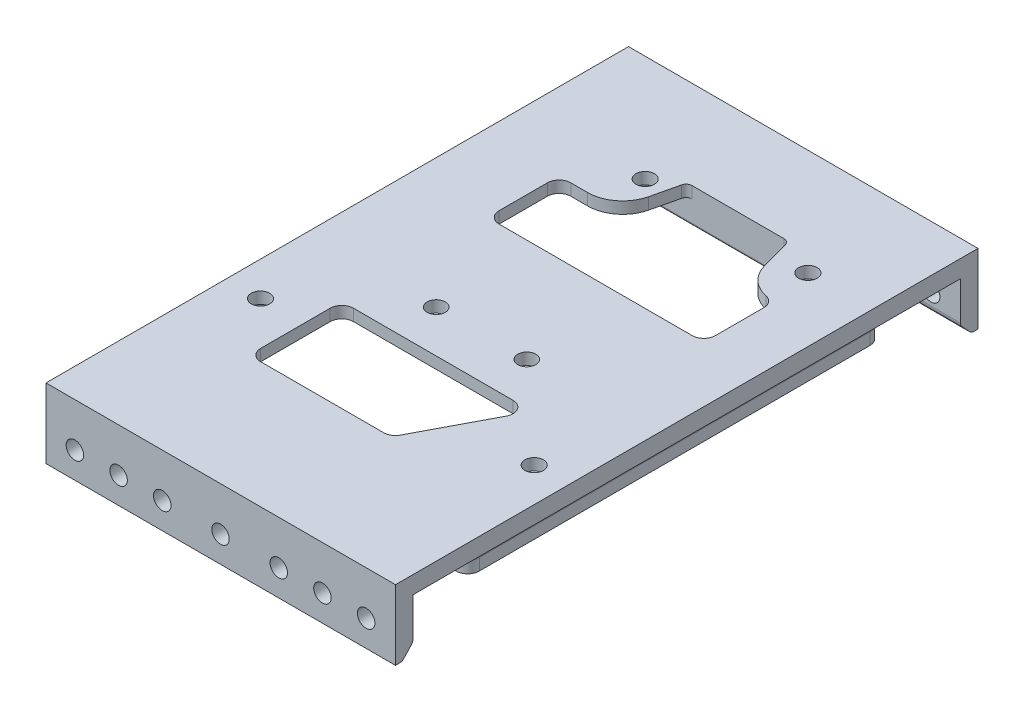
SolidWorks part; units mm, degrees
ref_plane "Front Plane" through (0, 0, 0) normal (0, 0, 1) x (1, 0, 0)
ref_plane "Top Plane" through (0, 0, 0) normal (0, 1, 0) x (1, 0, 0)
ref_plane "Right Plane" through (0, 0, 0) normal (1, 0, 0) x (0, 0, -1)
sketch "Sketch1" plane through (0, 0, 0) normal (0, 1, 0) x (1, 0, 0)
  line L0 (26.67, -34.29) -> (-26.67, -34.29)
  line L1 (26.67, -34.29) -> (26.67, 31.75)
  line L2 (21.59, 34.29) -> (-11.176, 34.29)
  line L3 (-26.67, -34.29) -> (-26.67, 31.75)
  line L4 (-26.67, 31.75) -> (-13.716, 31.75)
  line L5 (-13.716, 31.75) -> (-11.176, 34.29)
  line L6 (21.59, 34.29) -> (24.13, 31.75)
  line L7 (24.13, 31.75) -> (26.67, 31.75)
  line L8 (-27.17, 32.25) -> (-13.9231, 32.25)
  line L9 (-13.9231, 32.25) -> (-11.3831, 34.79)
  line L10 (21.7971, 34.79) -> (-11.3831, 34.79)
  line L11 (21.7971, 34.79) -> (24.3371, 32.25)
  line L12 (24.3371, 32.25) -> (27.17, 32.25)
  line L13 (27.17, -34.79) -> (27.17, 32.25)
  line L14 (27.17, -34.79) -> (-27.17, -34.79)
  line L15 (-27.17, -34.79) -> (-27.17, 32.25)
  line L16 (22.6255, 36.79) -> (-12.2115, 36.79)
  line L17 (30, -50) -> (-30, -50)
  line L18 (30, -50) -> (30, 50)
  line L19 (30, 50) -> (-30, 50)
  line L20 (-30, -50) -> (-30, 50)
  line L21 (30, -50) -> (-30, 50) construction
  line L22 (30, 50) -> (-30, -50) construction
  line L23 (-30, 50) -> (30, 50)
  line L24 (-30, 50) -> (-30, -50)
  line L25 (-30, -50) -> (30, -50)
  line L26 (30, 50) -> (30, -50)
  line L27 (-14.7515, 34.25) -> (-12.2115, 36.79)
  line L28 (-29.17, 34.25) -> (-14.7515, 34.25)
  line L29 (-29.17, -36.79) -> (-29.17, 34.25)
  line L30 (29.17, -36.79) -> (-29.17, -36.79)
  line L31 (29.17, -36.79) -> (29.17, 34.25)
  line L32 (25.1655, 34.25) -> (29.17, 34.25)
  line L33 (22.6255, 36.79) -> (25.1655, 34.25)
  circle A0 centre (19.05, 31.75) radius 1.5875
  circle A1 centre (-8.89, 31.75) radius 1.5875
  circle A2 centre (24.13, -20.32) radius 1.5875
  circle A3 centre (-24.13, -19.05) radius 1.5875
  point P24 (0, 0)
  dimension "D6" = 3.175
  dimension "D1" = 53.34
  dimension "D2" = 2.54
  dimension "D3" = 45
  dimension "D4" = 40.386
  dimension "D5" = 45
  dimension "D7" = 35.56
  dimension "D8" = 7.62
  dimension "D9" = 2.54
  dimension "D10" = 50.8
  dimension "D12" = 100
  dimension "D13" = 60
  dimension "D14" = 2
  dimension "D11" = 0.5
extrude "Boss-Extrude1" add sketch "Sketch1" along normal blind 3 contours L20 L17 L18 L19 L14 L15 L8 L9 L10 L11 L12 L13 | L20 L17 L18 L19 L16 L33 L32 L31 L30 L29 L28 L27 region at (23.2315, 0, -34.856) region at (0, 0, 48.8338)
sketch "Sketch3" plane through (0, 0, 0) normal (0, -1, 0) x (1, 0, 0)
  line L1 (30, 50) -> (-30, 50)
  line L2 (30, 50) -> (30, -50)
  line L3 (30, -50) -> (-30, -50)
  line L4 (-30, 50) -> (-30, -50)
extrude "Boss-Extrude2" add sketch "Sketch3" against normal blind 3
extrude "Cut-Extrude1" cut sketch "Sketch1<5>" along normal blind 1 contours L7 L6 L2 L5 L4 L3 L0 L1 A3 A2 A1 A0 | L15 L14 L13 L12 L11 L10 L9 L8 L6 L7 L1 L0 L3 L4 L5 L2 region at (0.1079, 0, 0.4765) region at (-20.5466, 0, -32.1617)
sketch "Sketch1<5>" plane through (0, 0, 0) normal (0, 1, 0) x (1, 0, 0) same geometry as "Sketch1"
extrude "Cut-Extrude2" cut sketch "Sketch1<6>" along normal through all contours A0 | A2 | A1 | A3 region at (19.05, 0, -31.75) region at (24.13, 0, 20.32)
sketch "Sketch1<6>" plane through (0, 0, 0) normal (0, 1, 0) x (1, 0, 0) same geometry as "Sketch1"
sketch "Sketch13" plane through (0, 0, 0) normal (0, -1, 0) x (1, 0, 0)
  line L0 (-30, 50) -> (-30, -50) construction
  line L1 (30, -50) -> (-30, -50)
  line L2 (30, -50) -> (30, -47)
  line L3 (30, -47) -> (-30, -47)
  line L4 (-30, -50) -> (-30, -47)
  dimension "D1" = 3
extrude "Boss-Extrude4" add sketch "Sketch13" along normal blind 9
sketch "Sketch15" plane through (0, 0, -47) normal (0, 0, 1) x (1, 0, 0)
  line L0 (30, 0) -> (30, -4.5)
  line L1 (30, -9) -> (30, 0) construction
  line L4 (0, -4.5) -> (0, 0)
  line L5 (30, 0) -> (-30, 0) construction
  circle A0 centre (-0.0404, -4.5072) radius 1.5
  circle A1 centre (9.9596, -4.5072) radius 1.5
  circle A2 centre (17.4596, -4.5072) radius 1.5
  circle A3 centre (24.9596, -4.5072) radius 1.5
  circle A4 centre (-25.0404, -4.5072) radius 1.5
  circle A5 centre (-17.5404, -4.5072) radius 1.5
  circle A6 centre (-10.0404, -4.5072) radius 1.5
extrude "Cut-Extrude3" cut sketch "Sketch15" against normal through all contours A3 | A2 | A0 | A6 | A5 | A4 | A1 region at (-0.0404, -4.5072, -47) region at (17.4596, -4.5072, -47) region at (24.9596, -4.5072, -47) region at (-25.0404, -4.5072, -47) region at (-17.5404, -4.5072, -47) region at (-10.0404, -4.5072, -47)
chamfer "Chamfer1" distance 2 angle 43 1 edges at (0, -9, -47) first distance on face at (11.4596, -4.5072, -47)
fillet "Fillet2" radius 1 2 edges at (0, -9, -48.865) (0, -7, -47)
sketch "Sketch18" plane through (0, 3, 0) normal (0, 1, 0) x (1, 0, 0)
  line L0 (-30, 50) -> (-30, 0)
  line L1 (-30, -50) -> (-30, 50) construction
  line L2 (-30, 0) -> (30, 0)
  line L3 (30, -50) -> (30, 50) construction
ref_plane "Plane4" through (0, 0, 0) normal (0, 0, 1) x (1, 0, 0)
mirror "Mirror2" about plane through (0, 0, 0) normal (0, 0, 1) of "Fillet2", "Chamfer1", "Cut-Extrude3", "Boss-Extrude4"
sketch "Sketch19" plane through (0, 1, 0) normal (0, -1, 0) x (-1, 0, 0)
  line L0 (-20.4296, -4.0512) -> (-7.6073, -28.4227)
  line L1 (-20.4296, 24.7983) -> (16.7119, 24.7983)
  line L2 (-20.4296, 24.7983) -> (-20.4296, -4.0512)
  line L3 (-7.6073, -28.4227) -> (16.7119, -28.4227)
  line L4 (16.7119, 24.7983) -> (16.7119, -28.4227)
  line L5 (7.0386, 24.7983) -> (4.6963, 34.79)
  line L6 (-21.7971, 34.79) -> (11.3831, 34.79) construction
  line L7 (4.6963, 34.79) -> (-12.7012, 34.79)
  line L8 (-12.7012, 34.79) -> (-15.4436, 24.7983)
  line M14 (11.3831, 34.79) -> (-21.7971, 34.79)
extrude "Cut-Extrude4" cut sketch "Sketch19" against normal through all contours L8 L1 L5 M14 | L4 L1 L2 L0 L3 region at (0.6318, 1, 0.2255) region at (4.1067, 1, -29.5818)
sketch "Sketch21" plane through (0, 3, 0) normal (0, 1, 0) x (1, 0, 0)
  line L0 (-30, 50) -> (-30, -50)
  line L1 (-30, 0) -> (30, 0)
  line L2 (30, 0) -> (30, 12.5)
  line L3 (30, -50) -> (30, 50) construction
  line L4 (0, 0) -> (0, 44.3456) construction
  line L5 (30, 12.5) -> (-30, 12.5)
  line L7 (30, -12.5) -> (-30, -12.5)
  line L8 (-30, 12.5) -> (-30, -12.5)
  line L9 (-10.5537, -7.874) -> (10.5537, -7.874)
  line L10 (-10.5537, -7.874) -> (-10.5537, 7.874)
  line L11 (-10.5537, 7.874) -> (10.5537, 7.874)
  line L12 (10.5537, -7.874) -> (10.5537, 7.874)
  line L13 (-10.5537, -7.874) -> (10.5537, 7.874) construction
  line L14 (-10.5537, 7.874) -> (10.5537, -7.874) construction
  line L15 (-30, 0) -> (0, 0)
  line L16 (30, 0) -> (30, -12.5)
  line L17 (30, 0) -> (30, -12.5)
  circle A0 centre (-7.7788, -5.2388) radius 1.5558
  circle A1 centre (7.7788, -5.2388) radius 1.5558
  point P14 (0, 0)
  line M8 (20.4296, 24.7983) -> (20.4296, -4.0512)
  line M10 (20.4296, -4.0512) -> (7.6073, -28.4227)
  line M14 (-16.7119, -28.4227) -> (-16.7119, 24.7983)
  dimension "D6" = 3.1115
  dimension "D2" = 25
  dimension "D3" = 60
  dimension "D4" = 21.1074
  dimension "D5" = 15.748
  dimension "D7" = 2.775
  dimension "D8" = 2.6353
extrude "Boss-Extrude5" add sketch "Sketch21" against normal blind 2 contours L12 L1 L5 L10 L11 M8 M14 | L12 L9 L10 L1 L7 M14 M10 M8 | L1 L12 L11 L10 | L9 L12 L1 L10 A0 A1 region at (1.8588, 3, -12.1081) region at (-13.6328, 3, 0.3919) region at (0, 3, -3.937) region at (0, 3, 3.8059)
extrude "Boss-Extrude6" add sketch "Sketch1<7>" against normal blind 3 contours L33 L16 L27 L28 L29 L30 L31 L32 L14 L15 L8 L9 L10 L11 L12 L13 region at (23.2315, 0, -34.856)
sketch "Sketch1<7>" plane through (0, 0, 0) normal (0, 1, 0) x (1, 0, 0) same geometry as "Sketch1"
fillet "Fillet1" radius 1 2 edges at (-13.9231, -1, -32.25) (24.3371, -1, -32.25)
fillet "Fillet4" radius 2 8 edges at (22.6255, -1.5, -36.79) (-12.2115, -1.5, -36.79) (-14.7515, -1.5, -34.25) (-29.17, -1.5, -34.25) (-29.17, -1.5, 36.79) (29.17, -1.5, 36.79) (25.1655, -1.5, -34.25) (29.17, -1.5, -34.25)
fillet "Fillet5" radius 2 8 edges at (-16.7119, 2, 28.4227) (7.6073, 2, 28.4227) (15.9846, 2, 12.5) (-16.7119, 2, 12.5) (20.4296, 2, -12.5) (20.4296, 2, -24.7983) (-16.7119, 2, -12.5) (-16.7119, 2, -24.7983)
fillet "Fillet6" radius 6 2 edges at (15.4436, 2, -24.7983) (-7.0386, 2, -24.7983)
fillet "Fillet7" radius 1 2 edges at (12.7012, 2, -34.79) (-4.6963, 2, -34.79)
fillet "Fillet8" radius 1 14 edges at (28.5842, 0, 36.2042) (0, 0, 36.79) (-28.5842, 0, 36.2042) (-28.5842, 0, -33.6642) (-21.375, 0, -34.25) (-14.8146, 0, -34.4022) (-13.4815, 0, -35.52) (-12.1485, 0, -36.6378) (5.207, 0, -36.79) (22.5625, 0, -36.6378) (23.8955, 0, -35.52) (25.2286, 0, -34.4022) (26.582, 0, -34.25) (28.5842, 0, -33.6642)
fillet "Fillet9" radius 0.4 10 edges at (24.3686, -3, -32.3261) (-13.9546, -3, -32.3261) (0, -3, 34.79) (-27.17, -3, 1.27) (-12.5067, -3, -33.6664) (5.207, -3, -34.79) (22.9207, -3, -33.6664) (25.9607, -3, -32.25) (27.17, -3, 1.27) (-20.7537, -3, -32.25)
